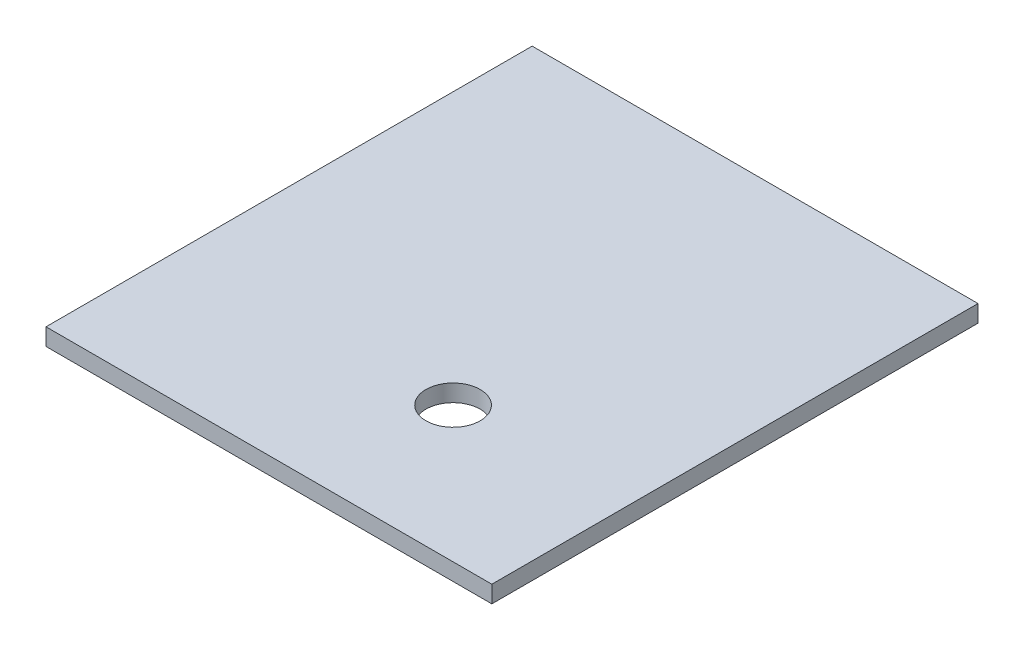
SolidWorks part; units mm, degrees
ref_plane "Front Plane" through (0, 0, 0) normal (0, 0, 1) x (1, 0, 0)
ref_plane "Top Plane" through (0, 0, 0) normal (0, 1, 0) x (1, 0, 0)
ref_plane "Right Plane" through (0, 0, 0) normal (1, 0, 0) x (0, 0, -1)
sketch "Sketch1" plane through (0, 0, 0) normal (0, 1, 0) x (1, 0, 0)
  line L1 (-73.025, -79.629) -> (73.025, -79.629)
  line L2 (-73.025, -79.629) -> (-73.025, 79.629)
  line L3 (-73.025, 79.629) -> (73.025, 79.629)
  line L4 (73.025, -79.629) -> (73.025, 79.629)
  line L5 (-73.025, -79.629) -> (73.025, 79.629) construction
  line L6 (-73.025, 79.629) -> (73.025, -79.629) construction
  point P0 (0, 0)
  dimension "D1" = 146.05
  dimension "D2" = 159.258
extrude "Boss-Extrude1" add sketch "Sketch1" along normal blind 5.588
sketch "Sketch4" plane through (0, 5.588, 0) normal (0, 1, 0) x (1, 0, 0)
  line L0 (-73.025, -79.629) -> (73.025, -79.629) construction
  line L1 (73.025, -79.629) -> (73.025, 79.629) construction
  circle A4 centre (15.875, -35.179) radius 8.89
  dimension "D1" = 17.78
  dimension "D2" = 44.45
  dimension "D3" = 57.15
extrude "Cut-Extrude1" cut sketch "Sketch4" against normal up to next
